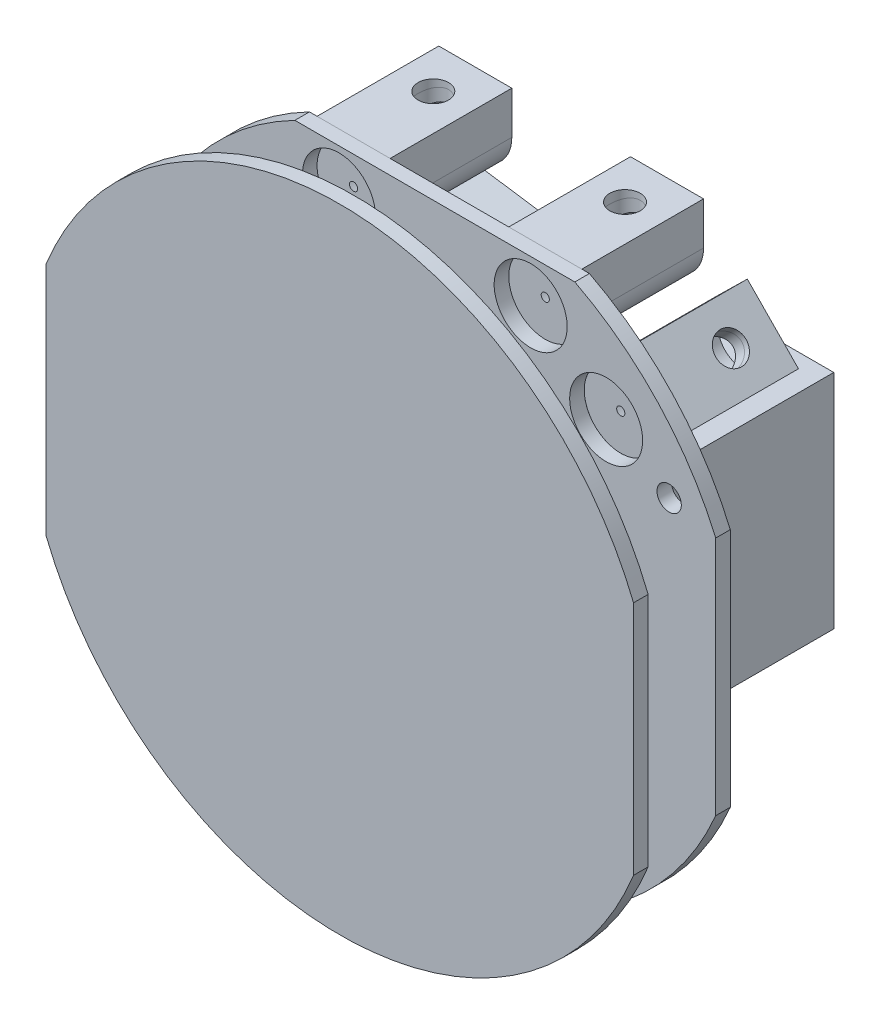
SolidWorks part; units mm, degrees
material "Custom Plastic"
ref_plane "Front Plane" through (0, 0, 0) normal (0, 0, 1) x (1, 0, 0)
ref_plane "Top Plane" through (0, 0, 0) normal (0, 1, 0) x (1, 0, 0)
ref_plane "Right Plane" through (0, 0, 0) normal (1, 0, 0) x (0, 0, -1)
sketch "Sketch1" plane through (0, 0, 0) normal (0, 0, 1) x (1, 0, 0)
  line L0 (0, -11.6056) -> (0, 12.1234) construction
  line L1 (-23.075, 22.3103) -> (23.075, 22.3103) construction
  line L2 (-23.075, 22.3103) -> (-23.075, -25.0997) construction
  line L3 (-23.075, -25.0997) -> (23.075, -25.0997) construction
  line L4 (23.075, 22.3103) -> (23.075, -25.0997) construction
  line L5 (-23.075, 9.8763) -> (-23.075, -9.8763)
  line L6 (23.075, 9.8763) -> (23.075, -9.8763)
  line L7 (-11.5, 22.3103) -> (11.5, 22.3103)
  line L8 (-28.4207, 10.8103) -> (35.7024, 10.8103) construction
  arc A0 (-23.075, -9.8763) -> (23.075, -9.8763) centre (0, 0) ccw
  arc A1 (23.075, 9.8763) -> (11.5, 22.3103) centre (0, 0) ccw
  arc A2 (-11.5, 22.3103) -> (-23.075, 9.8763) centre (0, 0) ccw
  circle A3 centre (-19.25, 10.8103) radius 1
  circle A4 centre (19.25, 10.8103) radius 1
  circle A5 centre (0, -22.3897) radius 1
  circle A6 centre (-19.25, 10.8103) radius 2 construction
  circle A7 centre (19.25, 10.8103) radius 2 construction
  circle A8 centre (0, -22.3897) radius 2 construction
  circle A9 centre (-14.075, 13.8103) radius 3
  circle A10 centre (-7.875, 18.8103) radius 3
  circle A11 centre (7.875, 18.8103) radius 3
  circle A12 centre (14.075, 13.8103) radius 3
  point P5 (0, -25.0997)
  point P10 (23.075, -9.8763)
  point P11 (23.075, 9.8763)
  point P12 (-11.5, 22.3103)
  point P13 (11.5, 22.3103)
  dimension "D8" = 2
  dimension "D10" = 4
  dimension "D14" = 6
  dimension "D1" = 46.15
  dimension "D2" = 47.41
  dimension "D3" = 23
  dimension "D6" = 11.5
  dimension "D7" = 19.25
  dimension "D9" = 33.2
  dimension "D15" = 9
  dimension "D16" = 8.5
  dimension "D17" = 15.2
  dimension "D18" = 3.5
  dimension "D4" = 15.2
  dimension "D5" = 3.5
extrude "Boss-Extrude1" add sketch "Sketch1" along normal blind 1.2
extrude "Boss-Extrude2" add sketch "Sketch1<2>" against normal blind 10 from surface separate body contours A10 | A9 | A11 | A12 region at (-14.075, 13.8103, 0) region at (-7.875, 18.8103, 0) region at (7.875, 18.8103, 0) region at (14.075, 13.8103, 0) starting at face at (0, 5.2359, 0)
sketch "Sketch1<2>" plane through (0, 0, 0) normal (0, 0, 1) x (1, 0, 0) same geometry as "Sketch1"
ref_plane "Plane1" through (0, 0, 9) normal (0, 0, -1) x (-1, 0, 0)
sketch "Sketch3" plane through (0, 0, 9) normal (0, 0, -1) x (-1, 0, 0)
  line L0 (-2.3692, 0) -> (5.499, 0) construction
  line L1 (-24.125, 24.125) -> (24.125, 24.125) construction
  line L2 (-24.125, 24.125) -> (-24.125, -24.125) construction
  line L3 (-24.125, -24.125) -> (24.125, -24.125) construction
  line L4 (24.125, 24.125) -> (24.125, -24.125) construction
  line L5 (0, 5.2769) -> (0, -2.3168) construction
  line L6 (-24.125, 9.6946) -> (-24.125, -9.6946)
  line L7 (24.125, 9.6946) -> (24.125, -9.6946)
  arc A0 (-24.125, -9.6946) -> (24.125, -9.6946) centre (0, 0) ccw
  arc A1 (24.125, 9.6946) -> (-24.125, 9.6946) centre (0, 0) ccw
  point P10 (24.125, 0)
  point P12 (0, -24.125)
  dimension "D1" = 52
  dimension "D2" = 48.25
extrude "Boss-Extrude4" add sketch "Sketch3" along normal blind 1.2 separate body
sketch "Sketch5" plane through (0, 0, -10) normal (0, 0, -1) x (-1, 0, 0)
  line L0 (-11.5, 22.3103) -> (11.5, 22.3103) construction
  line L1 (-14.075, 13.8103) -> (-20.2082, 19.8281) construction
  line L2 (-10.875, 18.8103) -> (-10.875, 22.3103)
  line L3 (-10.875, 22.3103) -> (-4.875, 22.3103)
  line L4 (-4.875, 18.8103) -> (-4.875, 22.3103)
  line L5 (-20.017, 15.4375) -> (-15.8148, 19.7203) construction
  line L6 (4.875, 18.8103) -> (4.875, 22.3103)
  line L7 (4.875, 22.3103) -> (10.875, 22.3103)
  line L8 (10.875, 18.8103) -> (10.875, 22.3103)
  line L9 (-15.8148, 19.7203) -> (-11.9739, 15.9516) construction
  line L10 (-20.017, 15.4375) -> (-16.1761, 11.6689) construction
  line L11 (-18.6743, 14.1202) -> (-14.4722, 18.4029)
  line L12 (-18.6743, 14.1202) -> (-16.1761, 11.6689)
  line L13 (-14.4722, 18.4029) -> (-11.9739, 15.9516)
  line L14 (11.9739, 15.9516) -> (15.8148, 19.7203) construction
  line L15 (15.8148, 19.7203) -> (20.017, 15.4375) construction
  line L16 (20.017, 15.4375) -> (16.1761, 11.6689) construction
  line L17 (14.075, 13.8103) -> (24.3489, 23.8909) construction
  line L18 (14.4722, 18.4029) -> (18.6743, 14.1202)
  line L19 (14.4722, 18.4029) -> (11.9739, 15.9516)
  line L20 (16.1761, 11.6689) -> (18.6743, 14.1202)
  circle A0 centre (-14.075, 13.8103) radius 3 construction
  circle A1 centre (-7.875, 18.8103) radius 3 construction
  circle A2 centre (7.875, 18.8103) radius 3 construction
  circle A3 centre (14.075, 13.8103) radius 3 construction
  circle A4 centre (-14.075, 13.8103) radius 3 construction
  circle A5 centre (-7.875, 18.8103) radius 3 construction
  circle A6 centre (7.875, 18.8103) radius 3 construction
  circle A7 centre (14.075, 13.8103) radius 3 construction
  arc A8 (-4.875, 18.8103) -> (-10.875, 18.8103) centre (-7.875, 18.8103) cw
  arc A9 (10.875, 18.8103) -> (4.875, 18.8103) centre (7.875, 18.8103) cw
  arc A10 (-11.5, 22.3103) -> (-23.075, 9.8763) centre (0, 0) ccw construction
  arc A11 (-11.5, 22.3103) -> (-23.075, 9.8763) centre (0, 0) ccw construction
  arc A12 (-11.9739, 15.9516) -> (-16.1761, 11.6689) centre (-14.075, 13.8103) cw
  arc A13 (23.075, 9.8763) -> (11.5, 22.3103) centre (0, 0) ccw construction
  arc A14 (23.075, 9.8763) -> (11.5, 22.3103) centre (0, 0) ccw construction
  arc A15 (16.1761, 11.6689) -> (11.9739, 15.9516) centre (14.075, 13.8103) cw
  circle A16 centre (-14.075, 13.8103) radius 3
  circle A17 centre (-7.875, 18.8103) radius 3
  circle A18 centre (7.875, 18.8103) radius 3
  circle A19 centre (14.075, 13.8103) radius 3
  point P28 (-17.9159, 17.5789)
  point P39 (17.9159, 17.5789)
  circle M1 centre (-7.875, 18.8103) radius 3
  dimension "D1" = 6
  dimension "D2" = 3.5
  dimension "D3" = 3.5
extrude "Boss-Extrude7" add sketch "Sketch5" against normal up to surface (10 mm away) separate body contours A16 L13 L11 L12 | L4 L3 L2 M1 | A18 L8 L7 L6 | A19 L20 L18 L19 region at (10.8055, 20.5603, -10) region at (-4.9445, 20.5603, -10) region at (16.5055, 16.195, -10) region at (-16.5055, 16.195, -10) up to face at (0, 5.2359, 0)
hole_wizard "Ø4.0mm Dowel Hole3" positions "3DSketch3" profile "Sketch8" hole size "Ø4.0" standard "ISO"
sketch3d "3DSketch3"
  line L0 (-14.075, 13.8103, -10) -> (-14.075, 13.8103, 0) construction
  line L1 (-7.875, 18.8103, -10) -> (-7.875, 18.8103, 0) construction
  line L2 (7.875, 18.8103, -10) -> (7.875, 18.8103, 0) construction
  line L3 (14.075, 13.8103, -10) -> (14.075, 13.8103, 0) construction
  point P0 (-14.075, 13.8103, -10)
  point P4 (-7.875, 18.8103, -10)
  point P8 (7.875, 18.8103, -10)
  point P12 (14.075, 13.8103, -10)
sketch "Sketch8" plane through (-14.075, 13.8103, -10) normal (1, 0, 0) x (0, 1, 0)
  line L0 (0, 0) -> (0, 10.2017)
  line L1 (0, 10.2017) -> (2, 9)
  line L2 (2, 9) -> (2, 0)
  line L5 (2, 0) -> (0, 0)
  line L10 (0, 10.2017) -> (-2, 9) construction
  line L11 (0, -6.35) -> (0, 107.95) construction
  dimension "Hole Dia." = 4
  dimension "Hole Depth" = 9
  dimension "Drill Angle" = 118
sketch "Sketch9" plane through (0, 0, 0) normal (0, 0, -1) x (-1, 0, 0)
  line L0 (-40.3168, 10.8103) -> (-7.2651, 10.8103) construction
  line L1 (-16.075, 9.8103) -> (-6.075, 9.8103)
  line L2 (-16.075, 9.8103) -> (-16.075, -8.4397)
  line L3 (-16.075, -8.4397) -> (-6.075, -8.4397)
  line L4 (-6.075, 9.8103) -> (-6.075, -8.4397)
  line L5 (-23.075, -9.8763) -> (-23.075, 9.8763) construction
  line L6 (16.725, 10.4603) -> (19.375, -7.5963)
  line L7 (19.375, -7.5963) -> (9.481, -9.0484)
  line L8 (9.481, -9.0484) -> (6.831, 9.0082)
  line L9 (6.831, 9.0082) -> (16.725, 10.4603)
  line L10 (-11.5, 22.3103) -> (11.5, 22.3103) construction
  line L12 (23.075, 9.8763) -> (23.075, -9.8763) construction
  circle A0 centre (-14.075, 13.8103) radius 3 construction
  circle A1 centre (-14.075, 13.8103) radius 3 construction
  circle A2 centre (14.075, 13.8103) radius 0.3357 construction
  dimension "D1" = 18.25
  dimension "D2" = 10
  dimension "D3" = 2
  dimension "D4" = 7
  dimension "D5" = 39.8
  dimension "D6" = 11.85
  dimension "D7" = 2.65
  dimension "D8" = 3.35
  dimension "D9" = 10
  dimension "D10" = 18.25
  dimension "D11" = 3.7
extrude "Boss-Extrude8" add sketch "Sketch9" along normal blind 15.5
sketch "Sketch11" plane through (16.5733, 16.2615, 0) normal (0.7138, 0.7004, 0) x (0, 0, -1)
  line L0 (10, 0) -> (0, 0) construction
  line L1 (10, -3) -> (10, 3) construction
  line L2 (0, -3) -> (0, 3) construction
  point P6 (6.55, 0)
  dimension "D1" = 3.45
sketch "Sketch12" plane through (0, 22.3103, 0) normal (0, 1, 0) x (1, 0, 0)
  line L0 (7.875, 10) -> (7.875, 0) construction
  line L1 (10.875, 10) -> (4.875, 10) construction
  line L2 (10.875, 0) -> (4.875, 0) construction
  line L3 (-7.875, 10) -> (-7.875, 0) construction
  line L4 (-4.875, 10) -> (-10.875, 10) construction
  line L5 (-4.875, 0) -> (-10.875, 0) construction
  point P6 (7.875, 6.55)
  point P13 (-7.875, 6.55)
  dimension "D1" = 3.45
  dimension "D2" = 3.45
sketch "Sketch13" plane through (-16.5733, 16.2615, 0) normal (-0.7138, 0.7004, 0) x (0, 0, 1)
  line L0 (-10, 0) -> (0, 0) construction
  line L1 (-10, 3) -> (-10, -3) construction
  line L2 (0, 3) -> (0, -3) construction
  point P6 (-6.55, 0)
  dimension "D1" = 3.45
hole_wizard "Ø2.5 (2.5) Diameter Hole1" positions "3DSketch5" profile "Sketch14" hole size "Ø2.5" standard "ISO"
sketch3d "3DSketch5"
  point P0 (16.5733, 16.2615, -6.55)
  point P3 (7.875, 22.3103, -6.55)
  point P6 (-7.875, 22.3103, -6.55)
  point P9 (-16.5733, 16.2615, -6.55)
sketch "Sketch14" plane through (16.5733, 16.2615, -6.55) normal (0, 0, 1) x (-0.7004, 0.7138, 0)
  line L0 (0, 0) -> (0, 3.7511)
  line L1 (0, 3.7511) -> (1.25, 3)
  line L2 (1.25, 3) -> (1.25, 0)
  line L5 (1.25, 0) -> (0, 0)
  line L10 (0, 3.7511) -> (-1.25, 3) construction
  line L11 (0, -6.35) -> (0, 107.95) construction
  dimension "Hole Dia." = 2.5
  dimension "Hole Depth" = 3
  dimension "Drill Angle" = 118
equation "\"D7@Sketch1\"=38.5/2"
equation "\"D4@Sketch1\"=\"D17@Sketch1\""
equation "\"D5@Sketch1\"=\"D18@Sketch1\""
equation "\"D9@Sketch9\"=\"D2@Sketch9\""
equation "\"D10@Sketch9\"=\"D1@Sketch9\""
